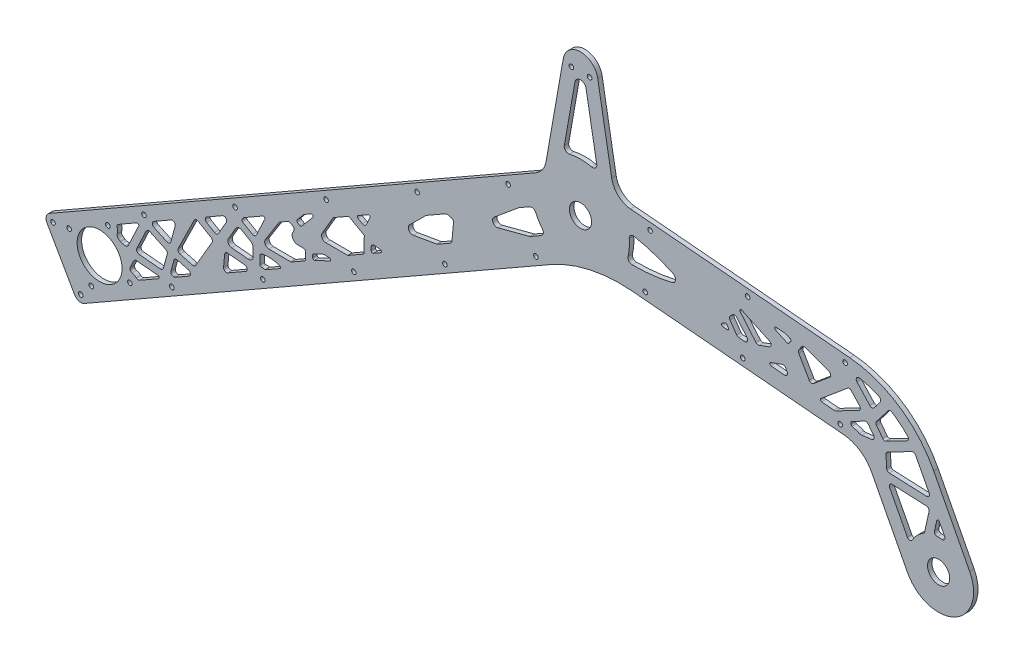
SolidWorks part; units mm, degrees
material "6061-T6 (SS)"
ref_plane "Front Plane" through (0, 0, 0) normal (0, 0, 1) x (1, 0, 0)
ref_plane "Top Plane" through (0, 0, 0) normal (0, 1, 0) x (1, 0, 0)
ref_plane "Right Plane" through (0, 0, 0) normal (1, 0, 0) x (0, 0, -1)
sketch "Reference Sketch" plane through (0, 0, 0) normal (0, 0, 1) x (1, 0, 0)
  line L0 (-343.92, -196.825) -> (0, 0) construction
  line L1 (-243.92, 103.175) -> (356.08, 103.175) construction
  line L2 (-243.92, 103.175) -> (-243.92, 0) construction
  line L3 (-243.92, 0) -> (356.08, 0) construction
  line L4 (356.08, 103.175) -> (356.08, 0) construction
  line L5 (0, 0) -> (256.08, -92.7116) construction
  line L6 (256.08, -92.7116) -> (56.08, -196.825) construction
  line L7 (256.08, -92.7116) -> (456.08, -196.825) construction
  line L8 (-343.92, -196.825) -> (56.08, -196.825) construction
  line L9 (56.08, -196.825) -> (456.08, -196.825) construction
  circle A1 centre (-343.92, -196.825) radius 100 construction
  circle A2 centre (56.08, -196.825) radius 100 construction
  circle A3 centre (456.08, -196.825) radius 100 construction
  circle A4 centre (-343.92, -196.825) radius 16.05 construction
  circle A5 centre (-343.92, -196.825) radius 28.55 construction
  circle A6 centre (-343.92, -196.825) radius 38.55 construction
  circle A7 centre (-343.92, -196.825) radius 33.55 construction
  point P13 (-343.92, -296.825)
  point P14 (556.08, -196.825)
  point P17 (-443.92, -196.825)
  dimension "D3" = 32.1
  dimension "D5" = 200
  dimension "D9" = 57.1
  dimension "D10" = 10
  dimension "D11" = 5
  dimension "D1" = 600
  dimension "D2" = 103.175
  dimension "D4" = 243.92
  dimension "D6" = 125
  dimension "D7" = 400
  dimension "D8" = 1000
sketch "Sketch2" plane through (0, 0, 0) normal (0, 0, 1) x (1, 0, 0)
  line L0 (-379.7168, -188.5069) -> (-32.0065, 10.4873)
  line L1 (-354.8814, -231.9028) -> (-21.5627, -41.1449)
  line L2 (-343.92, -196.825) -> (0, 0) construction
  line L3 (-184.3777, -76.7146) -> (-159.5423, -120.1104) construction
  line L4 (-24.685, 20.9013) -> (-12.3101, 91.0831)
  line L5 (12.3101, 91.0831) -> (22.322, 34.3028)
  line L6 (0, 98.4125) -> (0, 112.7) construction
  line L7 (-5.4848, 79.4125) -> (5.4848, 79.4125) construction
  line L8 (5.4848, 79.4125) -> (10.9697, 88.9125) construction
  line L9 (10.9697, 88.9125) -> (5.4848, 98.4125) construction
  line L10 (5.4848, 98.4125) -> (-5.4848, 98.4125) construction
  line L11 (-5.4848, 98.4125) -> (-10.9697, 88.9125) construction
  line L12 (-10.9697, 88.9125) -> (-5.4848, 79.4125) construction
  line L13 (-243.92, 103.175) -> (356.08, 103.175) construction
  line L14 (0, 88.9125) -> (0, 0) construction
  line L15 (35.7868, 21.9646) -> (192.5861, 8.2464)
  line L16 (252.5753, -31.8371) -> (278.2553, -81.1679)
  line L17 (233.9047, -104.2553) -> (208.2247, -54.9245)
  line L18 (36.8237, -28.3172) -> (188.2284, -41.5633)
  line L19 (0, 0) -> (192.5861, -16.8491) construction
  line L21 (-365.6311, -190.9191) -> (-338.0141, -175.1139) construction
  line L22 (-381.5729, -195.33) -> (-361.7045, -230.0467)
  line L23 (256.08, -92.7116) -> (56.08, -196.825) construction
  line L25 (-243.92, 0) -> (356.08, 0) construction
  circle A0 centre (0, 0) radius 7.9375
  circle A1 centre (-343.92, -196.825) radius 16.05
  arc A3 (-12.3101, 91.0831) -> (12.3101, 91.0831) centre (0, 88.9125) cw
  circle A4 centre (0, 88.9125) radius 6.5 construction
  circle A5 centre (-6.5, 88.9125) radius 1.65
  circle A6 centre (6.5, 88.9125) radius 1.65
  circle A7 centre (0, 88.9125) radius 9.5 construction
  arc A8 (252.5753, -31.8371) -> (192.5861, 8.2464) centre (186.0495, -66.4682) ccw
  circle A9 centre (256.08, -92.7116) radius 7.9375
  arc A10 (278.2553, -81.1679) -> (233.9047, -104.2553) centre (256.08, -92.7116) cw
  arc A11 (-21.5627, -41.1449) -> (36.8237, -28.3172) centre (28.1082, -127.9366) cw
  arc A12 (188.2284, -41.5633) -> (208.2247, -54.9245) centre (186.0495, -66.4682) cw
  arc A13 (22.322, 34.3028) -> (35.7868, 21.9646) centre (37.0941, 36.9075) ccw
  arc A14 (-32.0065, 10.4873) -> (-24.685, 20.9013) centre (-39.4572, 23.506) ccw
  circle A17 centre (-343.92, -196.825) radius 22.5 construction
  circle A18 centre (-365.6311, -190.9191) radius 1.65
  circle A19 centre (-338.0141, -175.1139) radius 1.65
  circle A20 centre (-322.2089, -202.7309) radius 1.65
  circle A21 centre (-349.8259, -218.5361) radius 1.65
  arc A27 (-379.7168, -188.5069) -> (-381.5729, -195.33) centre (-377.2333, -192.8465) ccw
  arc A28 (-361.7045, -230.0467) -> (-354.8814, -231.9028) centre (-357.3649, -227.5632) ccw
  circle A29 centre (-343.92, -196.825) radius 33.55 construction
  circle A32 centre (-343.92, -196.825) radius 38.55 construction
  point P16 (-171.96, -98.4125)
  point P64 (-343.92, -196.825)
  dimension "D1" = 15.875
  dimension "D2" = 32.1
  dimension "D3" = 45
  dimension "D5" = 13
  dimension "D6" = 3.3
  dimension "D7" = 6
  dimension "D12" = 50
  dimension "D14" = 100
  dimension "D16" = 15
  dimension "D17" = 5
  dimension "D18" = 25
  dimension "D19" = 3.3
  dimension "D15" = 4
  dimension "D4" = 50
  dimension "D8" = 19
  dimension "D9" = 14.2875
  dimension "D10" = 9.525
  dimension "D11" = 10
  dimension "D13" = 50
extrude "Base" add sketch "Sketch2" along normal blind 3.175
sketch "Sketch3" plane through (0, 0, 3.175) normal (0, 0, 1) x (1, 0, 0)
  line L0 (-343.92, -196.825) -> (0, 0) construction
  line L5 (0, 0) -> (197.3986, -17.2701) construction
  line L6 (192.5861, 8.2464) -> (35.7868, 21.9646) construction
  line L9 (36.8237, -28.3172) -> (188.2284, -41.5633) construction
  line L10 (-31.8958, -41.2976) -> (0, 0) construction
  line L11 (0, 0) -> (46.2693, -24.1244) construction
  circle A0 centre (-357.3649, -227.5632) radius 1.65
  circle A1 centre (-343.92, -196.825) radius 33.55 construction
  arc A2 (-361.7045, -230.0467) -> (-354.8814, -231.9028) centre (-357.3649, -227.5632) ccw construction
  circle A3 centre (-292.2711, -190.3101) radius 1.65
  circle A4 centre (-227.1773, -153.057) radius 1.65
  circle A5 centre (-162.0835, -115.8038) radius 1.65
  circle A6 centre (-96.9897, -78.5507) radius 1.65
  circle A7 centre (-31.8958, -41.2976) radius 1.65
  circle A8 centre (-312.1394, -155.5934) radius 1.65
  circle A9 centre (-377.2333, -192.8465) radius 1.65
  circle A10 centre (-247.0456, -118.3403) radius 1.65
  circle A11 centre (-181.9518, -81.0871) radius 1.65
  circle A12 centre (-116.858, -43.834) radius 1.65
  circle A13 centre (-51.7642, -6.5809) radius 1.65
  circle A14 centre (46.2693, -24.1244) radius 1.65
  circle A15 centre (116.0029, -30.2253) radius 1.65
  circle A16 centre (185.7366, -36.3262) radius 1.65
  circle A17 centre (189.2228, 3.5215) radius 1.65
  circle A18 centre (119.4892, 9.6224) radius 1.65
  circle A19 centre (49.7555, 15.7234) radius 1.65
  dimension "D1" = 3.3
  dimension "D2" = 6
  dimension "D3" = 5
  dimension "D5" = 3
  dimension "D4" = 75
  dimension "D6" = 70
extrude "Strut Holes" cut sketch "Sketch3" against normal through all
sketch "Sketch6" plane through (0, 0, 3.175) normal (0, 0, 1) x (1, 0, 0)
  line L0 (-315.2692, -197.7109) -> (-301.7593, -189.9792)
  line L1 (-354.8814, -231.9028) -> (-21.5627, -41.1449) construction
  line L2 (-289.845, -183.1607) -> (-279.9388, -177.4914)
  line L3 (-225.0683, -146.089) -> (-215.0659, -140.3647)
  line L4 (-202.4189, -105.5114) -> (-200.6862, -106.5205)
  line L5 (-330.4255, -170.6672) -> (-317.3783, -163.2003)
  line L6 (-32.0065, 10.4873) -> (-379.7168, -188.5069) construction
  line L7 (-315.9769, -164.4942) -> (-323.4022, -180.2613)
  line L8 (-325.3934, -181.4009) -> (-327.8261, -181.1787)
  line L9 (-302.165, -188.1154) -> (-317.5291, -186.7124)
  line L10 (-319.5204, -187.852) -> (-321.9207, -192.9489)
  line L11 (-295.5333, -171.6316) -> (-298.2962, -181.7883)
  line L12 (-300.4079, -183.2551) -> (-315.6625, -181.8621)
  line L13 (-317.2901, -179.0183) -> (-310.6415, -164.9005)
  line L14 (-307.9799, -163.9432) -> (-296.6111, -169.2972)
  line L15 (-280.4073, -173.8257) -> (-288.2923, -171.6808)
  line L16 (-290.7472, -173.0857) -> (-292.8686, -180.8843)
  line L17 (-292.7787, -149.122) -> (-305.2156, -156.2396)
  line L18 (-305.0743, -159.7848) -> (-295.766, -164.1685)
  line L19 (-292.984, -162.8841) -> (-289.8554, -151.3828)
  line L20 (-286.4122, -167.0105) -> (-277.4777, -169.4409)
  line L21 (-275.2245, -168.5176) -> (-263.487, -148.3649)
  line L22 (-264.2087, -145.6301) -> (-273.4911, -140.2238)
  line L23 (-276.2919, -141.0684) -> (-287.6814, -164.1971)
  line L24 (-267.3269, -134.556) -> (-255.9817, -128.0631)
  line L25 (-253.26, -130.8055) -> (-258.9575, -140.5878)
  line L26 (-261.6923, -141.3094) -> (-267.3401, -138.02)
  line L27 (-255.2613, -159.7424) -> (-254.4886, -151.2802)
  line L28 (-252.315, -149.4703) -> (-240.2297, -150.5739)
  line L29 (-292.2711, -190.3101) -> (-299.0066, -188.4038) construction
  line L30 (-252.2762, -161.6601) -> (-239.4181, -154.3014)
  line L31 (-246.5402, -131.1894) -> (-251.7948, -140.2114)
  line L32 (-249.4752, -144.7088) -> (-237.508, -145.8016)
  line L33 (-234.2352, -142.8254) -> (-234.2117, -136.6339)
  line L34 (-235.7018, -134.0302) -> (-242.4379, -130.1069)
  line L35 (-229.2226, -139.4963) -> (-229.2439, -145.1246)
  line L36 (-241.7536, -124.7193) -> (-234.6398, -128.8625)
  line L37 (-231.8238, -127.9864) -> (-225.7969, -115.1887)
  line L38 (-227.1983, -113.8948) -> (-240.4869, -121.4998)
  line L39 (-215.6688, -112.1749) -> (-225.38, -127.5855)
  line L40 (-222.8533, -132.1849) -> (-207.4544, -132.2434)
  line L41 (-206.4534, -131.9792) -> (-197.5057, -126.8584)
  line L42 (-196.4991, -125.1302) -> (-196.4845, -121.2849)
  line L43 (-198.4769, -119.2773) -> (-202.2607, -119.2629)
  line L44 (-205.6297, -113.1304) -> (-205.0269, -112.1739)
  line L45 (-205.7124, -109.3794) -> (-207.4618, -108.3605)
  line L46 (-209.4618, -108.3529) -> (-214.9702, -111.5053)
  line L47 (-223.2993, -137.1832) -> (-189.5978, -137.3112) construction
  line L48 (-199.4194, -106.3021) -> (-191.3609, -96.7721)
  line L49 (-192.6212, -95.2585) -> (-197.479, -98.0386)
  line L50 (-198.0128, -98.4831) -> (-202.6792, -104.0016)
  line L51 (-191.4798, -120.0542) -> (-191.4866, -121.8475)
  line L52 (-190.0674, -122.7592) -> (-179.2455, -117.7628)
  line L54 (-190.899, -119.1501) -> (-184.1308, -116.0253)
  line L55 (-183.2849, -115.8411) -> (-179.6609, -115.8549)
  line L56 (-166.4011, -107.9052) -> (-182.2049, -107.8452)
  line L57 (-184.7858, -103.3353) -> (-176.832, -89.6789)
  line L58 (-176.832, -89.6789) -> (-165.639, -83.2731)
  line L59 (-165.639, -83.2731) -> (-154.6405, -89.6789)
  line L60 (-154.6405, -89.6789) -> (-154.6842, -101.1996)
  line L61 (-154.6842, -101.1996) -> (-166.4011, -107.9052)
  line L62 (-176.832, -89.6789) -> (-166.4011, -107.9052) construction
  line L63 (-149.6667, -96.5998) -> (-149.6576, -94.1811)
  line L64 (-147.4757, -92.197) -> (-143.2847, -92.5797)
  line L65 (-142.8789, -94.4434) -> (-148.17, -97.4715)
  line L66 (-159.1247, -79.5451) -> (-152.014, -75.4756)
  line L67 (-150.6126, -76.7696) -> (-153.1821, -82.2258)
  line L68 (-155.9981, -83.102) -> (-159.1313, -81.2771)
  line L69 (-154.1121, -84.2004) -> (-149.6493, -91.9985) construction
  line L70 (-90.8199, -49.6985) -> (-91.8964, -61.4879)
  line L71 (-93.3939, -63.8188) -> (-101.9943, -68.7409)
  line L72 (-102.9747, -69.0935) -> (-119.6299, -71.9651)
  line L73 (-122.2529, -66.8794) -> (-110.6811, -55.3952)
  line L74 (-110.058, -54.9208) -> (-96.7247, -47.2901)
  line L75 (-94.4471, -46.9991) -> (-92.2866, -47.5868)
  line L76 (-102.4534, -69.0036) -> (-110.4008, -55.117) construction
  line L78 (-28.0968, -26.4494) -> (-35.8254, -30.8725)
  line L79 (-36.5501, -31.1694) -> (-59.134, -37.129)
  line L80 (-61.819, -31.9228) -> (-44.3172, -17.3499)
  line L81 (-43.8877, -17.0516) -> (-36.2746, -12.6946)
  line L82 (-44.1155, -17.182) -> (-36.1682, -31.0687) construction
  line L83 (-11.5997, 37.5245) -> (-3.9861, 80.7029)
  line L84 (3.9861, 80.7029) -> (11.5997, 37.5245)
  line L85 (22.322, 34.3028) -> (12.3101, 91.0831) construction
  line L86 (-12.3101, 91.0831) -> (-24.685, 20.9013) construction
  line L87 (192.5861, 8.2464) -> (35.7868, 21.9646) construction
  line L88 (36.8237, -28.3172) -> (188.2284, -41.5633) construction
  line L89 (-227.1773, -153.057) -> (-233.9128, -151.1507) construction
  line L90 (246.076, -72.9136) -> (249.254, -58.5784)
  line L91 (247.3887, -56.1475) -> (222.9622, -55.081)
  line L92 (221.1009, -58.0026) -> (233.7353, -82.273)
  line L93 (208.2247, -54.9245) -> (233.9047, -104.2553) construction
  line L94 (253.1337, -68.7997) -> (254.752, -61.5)
  line L95 (256.6153, -61.2547) -> (260.3456, -68.4206)
  line L96 (278.2553, -81.1679) -> (252.5753, -31.8371) construction
  line L97 (249.3108, -47.2228) -> (239.5975, -28.5637)
  line L98 (236.9, -27.7132) -> (219.5656, -36.7369)
  line L99 (218.491, -38.5982) -> (218.8608, -47.0688)
  line L100 (220.7717, -48.9796) -> (247.4495, -50.1444)
  line L101 (233.4135, -22.7639) -> (218.6181, -30.4658)
  line L102 (216.1079, -29.9093) -> (211.6718, -24.1281)
  line L103 (211.6718, -21.693) -> (220.0072, -10.8302)
  line L104 (209.6166, -31.3057) -> (205.7463, -26.2618)
  line L105 (203.2361, -25.7053) -> (194.0101, -30.5081)
  line L106 (193.4718, -31.3951) -> (193.4718, -32.4967)
  line L107 (201.069, -35.4569) -> (208.2909, -34.5061)
  line L108 (214.3031, -8.4078) -> (209.9577, -14.0708)
  line L109 (197.6887, -4.156) -> (206.8964, -14.2045)
  line L110 (193.6814, -11.6243) -> (199.5455, -18.0239)
  line L111 (198.9945, -21.1491) -> (182.8075, -29.5754)
  line L112 (181.1608, -29.903) -> (172.4826, -29.1438)
  line L113 (171.927, -27.3815) -> (190.9213, -11.4434)
  line L114 (178.1992, -11.0225) -> (166.5918, -20.7623)
  line L115 (163.5742, -20.2302) -> (156.048, -7.1944)
  line L116 (156.1417, -5.0472) -> (158.1885, -2.1242)
  line L117 (160.5108, -1.3919) -> (177.5977, -7.611)
  line L118 (146.6448, -20.9077) -> (147.747, -22.8167)
  line L119 (145.8406, -25.8091) -> (136.23, -24.9682)
  line L120 (135.9751, -23.0324) -> (144.2287, -20.0283)
  line L121 (134.9743, -13.819) -> (127.6718, -16.4769)
  line L122 (125.4557, -15.8831) -> (114.1985, -2.4673)
  line L123 (115.3872, -0.9182) -> (135.1355, -10.127)
  line L124 (139.4306, -1.096) -> (147.8318, -5.0136)
  line L125 (149.0736, -4.6809) -> (150.4259, -2.7496)
  line L126 (149.9488, -1.2363) -> (146.0985, 0.1651)
  line L127 (145.3339, 0.3346) -> (139.9404, 0.8065)
  line L128 (111.6605, -7.2212) -> (119.0455, -16.0223)
  line L129 (117.3391, -19.3002) -> (113.1162, -18.9308)
  line L130 (111.6522, -18.0855) -> (106.8775, -11.2665)
  line L131 (107.1016, -8.7052) -> (108.7142, -7.0926)
  line L132 (104.7039, -15.1361) -> (105.7554, -16.6377)
  line L133 (104.8491, -18.2075) -> (101.6773, -17.93)
  line L134 (101.2644, -16.0678) -> (103.3847, -14.8436)
  arc A0 (-317.584, -197.4764) -> (-320.5599, -195.9279) centre (-322.2089, -202.7309) ccw
  arc A1 (-291.1568, -183.3993) -> (-291.2348, -183.3872) centre (-292.2711, -190.3101) ccw
  arc A2 (-225.7665, -146.2006) -> (-228.1106, -146.1195) centre (-227.1773, -153.057) ccw
  arc A4 (-322.0747, -194.2209) -> (-322.0953, -194.053) centre (-343.92, -196.825) ccw
  arc A5 (-331.3132, -177.1382) -> (-331.3392, -173.0054) centre (-338.0141, -175.1139) ccw
  arc A6 (-329.0005, -180.6569) -> (-330.6088, -179.309) centre (-343.92, -196.825) ccw
  arc A8 (-227.5555, -137.5318) -> (-215.2363, -138.5515) centre (-223.3943, -162.1831) cw
  arc A9 (-241.9747, -123.1658) -> (-241.1717, -122.1478) centre (-247.0456, -118.3403) ccw
  arc A10 (-32.0383, -14.0906) -> (-27.2511, -21.9631) centre (0, 0) ccw
  arc A11 (-251.7948, -140.2114) -> (-249.4752, -144.7088) centre (-249.2024, -141.7213) ccw
  arc A12 (-225.38, -127.5855) -> (-222.8533, -132.1849) centre (-222.8419, -129.1849) ccw
  arc A13 (-182.2049, -107.8452) -> (-184.7858, -103.3353) centre (-182.1935, -104.8452) cw
  arc A14 (-119.6299, -71.9651) -> (-122.2529, -66.8794) centre (-120.1396, -69.0087) cw
  arc A15 (-59.134, -37.129) -> (-61.819, -31.9228) centre (-59.8994, -34.2283) cw
  arc A16 (-7.9627, 34.0822) -> (7.9627, 34.0822) centre (0, 0) cw
  arc A17 (-3.9861, 80.7029) -> (3.9861, 80.7029) centre (0, 80) cw
  arc A18 (34.8636, 3.0867) -> (34.0029, -8.2948) centre (0, 0) cw
  arc A19 (38.4335, 6.2944) -> (66.0977, -2.7713) centre (15.1723, -111.4295) cw
  arc A20 (66.0977, -2.7713) -> (65.4856, -8.7407) centre (64.749, -5.6491) cw
  arc A21 (36.898, -12.0057) -> (65.4856, -8.7407) centre (37.6733, 107.9918) ccw
  arc A22 (245.141, -74.2025) -> (237.26, -82.3165) centre (256.08, -92.7116) ccw
  arc A23 (258.3595, -71.3328) -> (255.1708, -71.2308) centre (256.08, -92.7116) ccw
  arc A24 (222.6875, -10.3732) -> (233.9189, -19.5905) centre (186.0495, -66.4682) cw
  arc A25 (252.5753, -31.8371) -> (192.5861, 8.2464) centre (186.0495, -66.4682) ccw construction
  arc A26 (194.2312, -33.4673) -> (199.4914, -35.2382) centre (186.0495, -66.4682) cw
  arc A27 (208.2247, -54.9245) -> (188.2284, -41.5633) centre (186.0495, -66.4682) ccw construction
  arc A28 (213.5369, -5.3663) -> (199.5667, -0.8459) centre (186.0495, -66.4682) ccw
  arc A29 (218.8608, -47.0688) -> (220.7717, -48.9796) centre (220.8589, -46.9815) ccw
  arc A30 (239.5975, -28.5637) -> (236.9, -27.7132) centre (237.8235, -29.4872) ccw
  arc A31 (219.5656, -36.7369) -> (218.491, -38.5982) centre (220.4891, -38.5109) ccw
  arc A32 (127.6718, -16.4769) -> (125.4557, -15.8831) centre (126.9878, -14.5975) cw
  arc A33 (-240.4869, -121.4998) -> (-241.1717, -122.1478) centre (-239.4934, -123.2356) ccw
  arc A34 (-234.6398, -128.8625) -> (-231.8238, -127.9864) centre (-233.6332, -127.1343) ccw
  arc A35 (-229.2226, -139.4963) -> (-227.5555, -137.5318) centre (-227.2226, -139.5039) cw
  arc A36 (-315.2692, -197.7109) -> (-317.584, -197.4764) centre (-316.2626, -195.9751) cw
  arc A37 (-322.0747, -194.2209) -> (-320.5599, -195.9279) centre (-320.0887, -193.9842) ccw
  arc A38 (-321.9207, -192.9489) -> (-322.0953, -194.053) centre (-320.1113, -193.801) ccw
  arc A39 (-317.5291, -186.7124) -> (-319.5204, -187.852) centre (-317.711, -188.7042) ccw
  arc A40 (-323.4022, -180.2613) -> (-325.3934, -181.4009) centre (-325.2116, -179.4092) cw
  arc A41 (-327.8261, -181.1787) -> (-329.0005, -180.6569) centre (-327.6442, -179.187) cw
  arc A42 (-331.3132, -177.1382) -> (-330.6088, -179.309) centre (-329.3986, -177.7166) ccw
  arc A43 (-330.4255, -170.6672) -> (-331.3392, -173.0054) centre (-329.4321, -172.403) ccw
  arc A44 (-315.6625, -181.8621) -> (-317.2901, -179.0183) centre (-315.4807, -179.8704) cw
  arc A45 (-298.2962, -181.7883) -> (-300.4079, -183.2551) centre (-300.226, -181.2634) cw
  arc A46 (-289.845, -183.1607) -> (-291.1568, -183.3993) centre (-290.8384, -181.4248) cw
  arc A47 (-292.8686, -180.8843) -> (-291.2348, -183.3872) centre (-290.9387, -181.4092) ccw
  arc A48 (-280.4073, -173.8257) -> (-279.9388, -177.4914) centre (-280.9322, -175.7556) cw
  arc A49 (-288.2923, -171.6808) -> (-290.7472, -173.0857) centre (-288.8173, -173.6107) ccw
  arc A50 (-295.5333, -171.6316) -> (-296.6111, -169.2972) centre (-297.4632, -171.1066) ccw
  arc A51 (-310.6415, -164.9005) -> (-307.9799, -163.9432) centre (-308.8321, -165.7526) cw
  arc A52 (-305.2156, -156.2396) -> (-305.0743, -159.7848) centre (-304.2222, -157.9754) ccw
  arc A53 (-292.7787, -149.122) -> (-289.8554, -151.3828) centre (-291.7853, -150.8578) cw
  arc A54 (-295.766, -164.1685) -> (-292.984, -162.8841) centre (-294.9139, -162.3591) ccw
  arc A55 (-286.4122, -167.0105) -> (-287.6814, -164.1971) centre (-285.8872, -165.0807) cw
  arc A56 (-277.4777, -169.4409) -> (-275.2245, -168.5176) centre (-276.9527, -167.511) ccw
  arc A57 (-263.487, -148.3649) -> (-264.2087, -145.6301) centre (-265.2153, -147.3583) ccw
  arc A58 (-273.4911, -140.2238) -> (-276.2919, -141.0684) centre (-274.4977, -141.952) ccw
  arc A59 (-267.3269, -134.556) -> (-267.3401, -138.02) centre (-266.3335, -136.2918) ccw
  arc A60 (-258.9575, -140.5878) -> (-261.6923, -141.3094) centre (-260.6857, -139.5812) cw
  arc A61 (-254.4886, -151.2802) -> (-252.315, -149.4703) centre (-252.4969, -151.462) cw
  arc A62 (-255.2613, -159.7424) -> (-252.2762, -161.6601) centre (-253.2696, -159.9243) ccw
  arc A63 (-239.4181, -154.3014) -> (-240.2297, -150.5739) centre (-240.4115, -152.5656) ccw
  arc A64 (-255.9817, -128.0631) -> (-253.26, -130.8055) centre (-254.9883, -129.7989) cw
  arc A65 (-207.4544, -132.2434) -> (-206.4534, -131.9792) centre (-207.4468, -130.2434) ccw
  arc A66 (-214.9702, -111.5053) -> (-215.6688, -112.1749) centre (-213.9767, -113.2412) ccw
  arc A67 (-207.4618, -108.3605) -> (-209.4618, -108.3529) centre (-208.4684, -110.0887) ccw
  arc A68 (-205.0269, -112.1739) -> (-205.7124, -109.3794) centre (-206.719, -111.1076) ccw
  arc A69 (-202.2607, -119.2629) -> (-205.6297, -113.1304) centre (-202.2456, -115.263) cw
  arc A70 (-196.4845, -121.2849) -> (-198.4769, -119.2773) centre (-198.4845, -121.2773) ccw
  arc A71 (-197.5057, -126.8584) -> (-196.4991, -125.1302) centre (-198.4991, -125.1226) ccw
  arc A72 (-184.1308, -116.0253) -> (-183.2849, -115.8411) centre (-183.2925, -117.8411) cw
  arc A73 (-197.479, -98.0386) -> (-198.0128, -98.4831) centre (-196.4856, -99.7744) ccw
  arc A74 (-149.6576, -94.1811) -> (-147.4757, -92.197) centre (-147.6576, -94.1887) cw
  arc A75 (-153.1821, -82.2258) -> (-155.9981, -83.102) centre (-154.9915, -81.3737) cw
  arc A76 (-90.8199, -49.6985) -> (-92.2866, -47.5868) centre (-92.8116, -49.5167) ccw
  arc A77 (111.6605, -7.2212) -> (108.7142, -7.0926) centre (110.1284, -8.5068) ccw
  arc A78 (106.8775, -11.2665) -> (107.1016, -8.7052) centre (108.5158, -10.1194) cw
  arc A79 (113.1162, -18.9308) -> (111.6522, -18.0855) centre (113.2905, -16.9384) cw
  arc A80 (119.0455, -16.0223) -> (117.3391, -19.3002) centre (117.5134, -17.3078) cw
  arc A81 (134.9743, -13.819) -> (135.1355, -10.127) centre (134.2903, -11.9396) ccw
  arc A82 (146.6448, -20.9077) -> (144.2287, -20.0283) centre (144.9128, -21.9077) ccw
  arc A83 (147.747, -22.8167) -> (145.8406, -25.8091) centre (146.0149, -23.8167) cw
  arc A84 (156.048, -7.1944) -> (156.1417, -5.0472) centre (157.78, -6.1944) cw
  arc A85 (158.1885, -2.1242) -> (160.5108, -1.3919) centre (159.8268, -3.2713) cw
  arc A86 (178.1992, -11.0225) -> (177.5977, -7.611) centre (176.9136, -9.4904) ccw
  arc A87 (166.5918, -20.7623) -> (163.5742, -20.2302) centre (165.3062, -19.2302) cw
  arc A88 (193.6814, -11.6243) -> (190.9213, -11.4434) centre (192.2068, -12.9755) ccw
  arc A89 (199.5455, -18.0239) -> (198.9945, -21.1491) centre (198.071, -19.375) cw
  arc A90 (209.9577, -14.0708) -> (206.8964, -14.2045) centre (208.371, -12.8533) cw
  arc A91 (213.5369, -5.3663) -> (214.3031, -8.4078) centre (212.7164, -7.1903) cw
  arc A92 (233.9189, -19.5905) -> (233.4135, -22.7639) centre (232.49, -20.9899) cw
  arc A93 (222.6875, -10.3732) -> (220.0072, -10.8302) centre (221.5939, -12.0477) ccw
  arc A94 (211.6718, -24.1281) -> (211.6718, -21.693) centre (213.2585, -22.9105) cw
  arc A95 (218.6181, -30.4658) -> (216.1079, -29.9093) centre (217.6946, -28.6918) cw
  arc A96 (205.7463, -26.2618) -> (203.2361, -25.7053) centre (204.1595, -27.4793) ccw
  arc A97 (209.6166, -31.3057) -> (208.2909, -34.5061) centre (208.0299, -32.5232) cw
  arc A98 (246.076, -72.9136) -> (245.141, -74.2025) centre (244.1234, -72.4807) cw
  arc A99 (249.254, -58.5784) -> (247.3887, -56.1475) centre (247.3014, -58.1456) ccw
  arc A100 (222.9622, -55.081) -> (221.1009, -58.0026) centre (222.8749, -57.0791) ccw
  arc A101 (233.7353, -82.273) -> (237.26, -82.3165) centre (235.5093, -81.3495) ccw
  arc A102 (260.3456, -68.4206) -> (258.3595, -71.3328) centre (258.5716, -69.344) cw
  arc A103 (253.1337, -68.7997) -> (255.1708, -71.2308) centre (255.0863, -69.2326) ccw
  arc A104 (249.3108, -47.2228) -> (247.4495, -50.1444) centre (247.5367, -48.1463) cw
  arc A105 (199.5667, -0.8459) -> (197.6887, -4.156) centre (199.1632, -2.8048) ccw
  arc A106 (-215.2363, -138.5515) -> (-215.0659, -140.3647) centre (-215.5626, -139.4968) cw
  arc A107 (-301.7593, -189.9792) -> (-302.165, -188.1154) centre (-302.256, -189.1113) ccw
  arc A108 (-317.3783, -163.2003) -> (-315.9769, -164.4942) centre (-316.8815, -164.0682) cw
  arc A109 (-225.7969, -115.1887) -> (-227.1983, -113.8948) centre (-226.7016, -114.7627) ccw
  arc A110 (-241.7536, -124.7193) -> (-241.9747, -123.1658) centre (-241.2503, -123.8551) cw
  arc A111 (-225.7665, -146.2006) -> (-225.0683, -146.089) centre (-225.565, -145.2211) ccw
  arc A112 (-229.2439, -145.1246) -> (-228.1106, -146.1195) centre (-228.2439, -145.1284) ccw
  arc A113 (-202.4189, -105.5114) -> (-202.6792, -104.0016) centre (-201.9156, -104.6473) cw
  arc A114 (-200.6862, -106.5205) -> (-199.4194, -106.3021) centre (-200.183, -105.6564) ccw
  arc A115 (-191.4798, -120.0542) -> (-190.899, -119.1501) centre (-190.4798, -120.058) cw
  arc A116 (-191.4866, -121.8475) -> (-190.0674, -122.7592) centre (-190.4866, -121.8513) ccw
  arc A117 (-191.3609, -96.7721) -> (-192.6212, -95.2585) centre (-192.1245, -96.1264) ccw
  arc A118 (-179.2455, -117.7628) -> (-179.6609, -115.8549) centre (-179.6647, -116.8549) ccw
  arc A119 (-152.014, -75.4756) -> (-150.6126, -76.7696) centre (-151.5173, -76.3435) cw
  arc A120 (-159.1247, -79.5451) -> (-159.1313, -81.2771) centre (-158.628, -80.413) ccw
  arc A121 (-149.6667, -96.5998) -> (-148.17, -97.4715) centre (-148.6667, -96.6036) ccw
  arc A122 (-143.2847, -92.5797) -> (-142.8789, -94.4434) centre (-143.3756, -93.5755) cw
  arc A123 (101.6773, -17.93) -> (101.2644, -16.0678) centre (101.7644, -16.9338) cw
  arc A124 (104.7039, -15.1361) -> (103.3847, -14.8436) centre (103.8847, -15.7096) ccw
  arc A125 (105.7554, -16.6377) -> (104.8491, -18.2075) centre (104.9362, -17.2113) cw
  arc A126 (114.1985, -2.4673) -> (115.3872, -0.9182) centre (114.9646, -1.8245) cw
  arc A127 (136.23, -24.9682) -> (135.9751, -23.0324) centre (136.3171, -23.972) cw
  arc A128 (139.4306, -1.096) -> (139.9404, 0.8065) centre (139.8532, -0.1897) cw
  arc A129 (172.4826, -29.1438) -> (171.927, -27.3815) centre (172.5698, -28.1476) cw
  arc A130 (194.0101, -30.5081) -> (193.4718, -31.3951) centre (194.4718, -31.3951) ccw
  arc A131 (193.4718, -32.4967) -> (194.2312, -33.4673) centre (194.4718, -32.4967) ccw
  arc A132 (254.752, -61.5) -> (256.6153, -61.2547) centre (255.7283, -61.7164) cw
  arc A133 (146.0985, 0.1651) -> (145.3339, 0.3346) centre (145.0724, -2.654) ccw
  arc A134 (199.4914, -35.2382) -> (201.069, -35.4569) centre (200.6774, -32.4826) ccw
  arc A135 (182.8075, -29.5754) -> (181.1608, -29.903) centre (181.4223, -26.9144) cw
  arc A136 (-7.9627, 34.0822) -> (-11.5997, 37.5245) centre (-8.6452, 37.0035) cw
  arc A137 (7.9627, 34.0822) -> (11.5997, 37.5245) centre (8.6452, 37.0035) ccw
  arc A138 (34.8636, 3.0867) -> (38.4335, 6.2944) centre (37.8519, 3.3513) cw
  arc A139 (34.0029, -8.2948) -> (36.898, -12.0057) centre (36.9174, -9.0058) ccw
  arc A140 (-35.8254, -30.8725) -> (-36.5501, -31.1694) centre (-37.3155, -28.2687) cw
  arc A141 (-44.3172, -17.3499) -> (-43.8877, -17.0516) centre (-42.3976, -19.6554) cw
  arc A142 (-32.0383, -14.0906) -> (-36.2746, -12.6946) centre (-34.7845, -15.2984) ccw
  arc A143 (-27.2511, -21.9631) -> (-28.0968, -26.4494) centre (-29.5869, -23.8456) cw
  arc A144 (-96.7247, -47.2901) -> (-94.4471, -46.9991) centre (-95.2346, -49.8939) cw
  arc A145 (-91.8964, -61.4879) -> (-93.3939, -63.8188) centre (-94.884, -61.2151) cw
  arc A146 (-110.6811, -55.3952) -> (-110.058, -54.9208) centre (-108.5679, -57.5245) cw
  arc A147 (-101.9943, -68.7409) -> (-102.9747, -69.0935) centre (-103.4845, -66.1371) cw
  arc A148 (-246.5402, -131.1894) -> (-242.4379, -130.1069) centre (-243.9478, -132.6992) cw
  arc A149 (-234.2117, -136.6339) -> (-235.7018, -134.0302) centre (-237.2117, -136.6225) ccw
  arc A150 (-237.508, -145.8016) -> (-234.2352, -142.8254) centre (-237.2352, -142.8141) ccw
  arc A151 (150.4259, -2.7496) -> (149.9488, -1.2363) centre (149.6067, -2.176) ccw
  arc A152 (147.8318, -5.0136) -> (149.0736, -4.6809) centre (148.2544, -4.1073) ccw
  point P98 (-116.858, -43.834)
  point P110 (-254.1648, -144.2806)
  point P113 (-228.2654, -132.1643)
  point P143 (34.9003, -2.6394)
  point P203 (218.9408, -48.8997)
  point P206 (238.674, -26.7897)
  point P211 (126.3559, -16.9559)
  point P214 (-240.9361, -121.7569)
  point P217 (-232.7537, -129.961)
  point P220 (-229.2164, -137.8704)
  point P229 (-318.9237, -186.5851)
  point P232 (-323.9988, -181.5282)
  point P235 (-328.5183, -181.1155)
  point P240 (-331.9839, -171.5591)
  point P247 (-290.5028, -183.5371)
  point P252 (-275.7482, -175.0931)
  point P255 (-290.2222, -171.1558)
  point P262 (-308.5502, -158.1479)
  point P265 (-288.588, -146.7237)
  point P268 (-293.6097, -165.184)
  point P271 (-288.7533, -166.3737)
  point P278 (-275.3444, -139.1443)
  point P281 (-270.3335, -136.2766)
  point P288 (-255.6107, -163.5684)
  point P294 (-249.5035, -124.3556)
  point P297 (-206.9185, -132.2454)
  point P300 (-215.403, -111.753)
  point P303 (-208.4596, -107.7794)
  point P308 (-209.4769, -119.2355)
  point P311 (-196.4769, -119.2849)
  point P314 (-196.5035, -126.2849)
  point P329 (110.2575, -5.5492)
  point P334 (112.1872, -18.8495)
  point P337 (122.1491, -19.721)
  point P340 (139.5116, -12.1676)
  point P345 (149.6679, -26.1439)
  point P350 (159.0687, -0.8671)
  point P353 (180.8529, -8.7958)
  point P356 (164.7659, -22.2944)
  point P363 (208.5067, -15.9618)
  point P366 (215.8118, -6.4415)
  point P369 (235.7568, -21.544)
  point P374 (210.7376, -22.9105)
  point P377 (217.1296, -31.2407)
  point P380 (204.7246, -24.9304)
  point P383 (211.7254, -34.054)
  point P390 (219.5014, -54.9299)
  point P393 (235.6626, -85.9753)
  point P396 (262.2729, -72.1228)
  point P401 (250.9103, -50.2955)
  point P406 (-213.2581, -139.3301)
  point P412 (-314.6256, -161.6249)
  point P415 (-224.4456, -112.3194)
  point P420 (-225.4089, -146.284)
  point P423 (-229.2487, -146.3704)
  point P426 (-203.4487, -104.9116)
  point P431 (-191.4774, -119.4171)
  point P434 (-191.4925, -123.4171)
  point P437 (-187.699, -92.4415)
  point P440 (-175.1502, -115.872)
  point P447 (-149.6733, -98.3319)
  point P450 (-140.1262, -92.8681)
  point P453 (98.5177, -17.6536)
  point P458 (106.9854, -18.3944)
  point P463 (131.7364, -24.5751)
  point P468 (170.0776, -28.9333)
  point P471 (193.4718, -30.7883)
  point P474 (193.4718, -33.2883)
  point P477 (255.3467, -58.8176)
  point P484 (182.0319, -29.9792)
  point P491 (34.2849, 7.0387)
  point P494 (32.91, -11.9136)
  point P505 (-24.8853, -24.6115)
  point P508 (-95.6462, -46.6729)
  point P511 (-92.0384, -63.0431)
  point P524 (-234.2477, -146.0993)
  point P527 (151.1734, -1.682)
  point P530 (148.5923, -5.3682)
  dimension "D1" = 14
  dimension "D2" = 10
  dimension "D3" = 2
  dimension "D5" = 22
  dimension "D6" = 9
  dimension "D12" = 5
  dimension "D19" = 7
  dimension "D31" = 7
  dimension "D40" = 25
  dimension "D44" = 19
  dimension "D62" = 5
  dimension "D92" = 35
  dimension "D96" = 3
  dimension "D97" = 10
  dimension "D100" = 15
  dimension "D104" = 30
  dimension "D105" = 120
  dimension "D107" = 43
  dimension "D116" = 65
  dimension "D117" = 8
  dimension "D127" = 9
  dimension "D128" = 6
  dimension "D171" = 2
  dimension "D172" = 1
  dimension "D173" = 3
  dimension "D174" = 1
  dimension "D175" = 4
  dimension "D7" = 35
  dimension "D8" = 35
  dimension "D9" = 20
  dimension "D10" = 22
  dimension "D11" = 20
  dimension "D13" = 5
  dimension "D14" = 45
  dimension "D15" = 45
  dimension "D16" = 17
  dimension "D17" = 15
  dimension "D18" = 5
  dimension "D20" = 55
  dimension "D21" = 5
  dimension "D22" = 45
  dimension "D23" = 23
  dimension "D24" = 34
  dimension "D25" = 60
  dimension "D26" = 5
  dimension "D27" = 5
  dimension "D28" = 5
  dimension "D29" = 30
  dimension "D30" = 24
  dimension "D32" = 55
  dimension "D33" = 35
  dimension "D34" = 25
  dimension "D35" = 5
  dimension "D36" = 6
  dimension "D37" = 60
  dimension "D38" = 5
  dimension "D39" = 20
  dimension "D41" = 11
  dimension "D42" = 35
  dimension "D43" = 60
  dimension "D45" = 19.5
  dimension "D46" = 5
  dimension "D47" = 5
  dimension "D48" = 30
  dimension "D49" = 5
  dimension "D50" = 14
  dimension "D51" = 13
  dimension "D52" = 8.5
  dimension "D53" = 60
  dimension "D54" = 12
  dimension "D55" = 7
  dimension "D56" = 22
  dimension "D57" = 28
  dimension "D58" = 60
  dimension "D59" = 15
  dimension "D60" = 8
  dimension "D61" = 13
  dimension "D63" = 12
  dimension "D64" = 20
  dimension "D65" = 5
  dimension "D66" = 65
  dimension "D67" = 25
  dimension "2" = 18
  dimension "D68" = 8
  dimension "D69" = 4
  dimension "D70" = 14
  dimension "D71" = 15
  dimension "D72" = 13.5
  dimension "D73" = 60
  dimension "D74" = 60
  dimension "D75" = 8
  dimension "D76" = 5
  dimension "D77" = 35
  dimension "D78" = 0.5076
  dimension "D79" = 5
  dimension "D80" = 11
  dimension "D81" = 35
  dimension "D82" = 16
  dimension "D83" = 18
  dimension "D84" = 55
  dimension "D85" = 45
  dimension "D86" = 20
  dimension "D87" = 15
  dimension "D88" = 12
  dimension "D89" = 17
  dimension "D90" = 16
  dimension "D91" = 18
  dimension "D93" = 15
  dimension "D94" = 10
  dimension "D95" = 13
  dimension "D98" = 10
  dimension "D99" = 80
  dimension "D101" = 16
  dimension "D102" = 22
  dimension "D103" = 22
  dimension "D106" = 7
  dimension "D108" = 10
  dimension "D109" = 40
  dimension "D110" = 10
  dimension "D111" = 6
  dimension "D112" = 60
  dimension "D113" = 35
  dimension "D114" = 15
  dimension "D115" = 6
  dimension "D118" = 26.5
  dimension "D119" = 6
  dimension "D120" = 85
  dimension "D121" = 85
  dimension "D122" = 32
  dimension "D123" = 21
  dimension "D124" = 80
  dimension "D125" = 75
  dimension "D126" = 6
  dimension "D129" = 10.5
  dimension "D130" = 80
  dimension "D131" = 12
  dimension "D132" = 8
  dimension "D133" = 6
  dimension "D134" = 2.5
  dimension "D135" = 100
  dimension "D136" = 11.5
  dimension "D137" = 60
  dimension "D138" = 11
  dimension "D139" = 45
  dimension "D140" = 12
  dimension "D141" = 8.5
  dimension "D142" = 12
  dimension "D143" = 18
  dimension "D144" = 80
  dimension "D145" = 21
  dimension "D146" = 60
  dimension "D147" = 60
  dimension "D148" = 15
  dimension "D149" = 12
  dimension "D150" = 18
  dimension "D151" = 25
  dimension "D152" = 9
  dimension "D153" = 12
  dimension "D154" = 6
  dimension "D155" = 15
  dimension "D156" = 20
  dimension "D157" = 10
  dimension "D158" = 13.5
  dimension "D159" = 4.5
  dimension "D160" = 45
  dimension "D161" = 14
  dimension "D162" = 5
  dimension "D163" = 10
  dimension "D164" = 16
  dimension "D165" = 50
  dimension "D166" = 18.5
  dimension "D167" = 50
  dimension "D168" = 4
  dimension "D169" = 8.5
  dimension "D170" = 35
extrude "Lightening Holes" cut sketch "Sketch6" against normal through all
